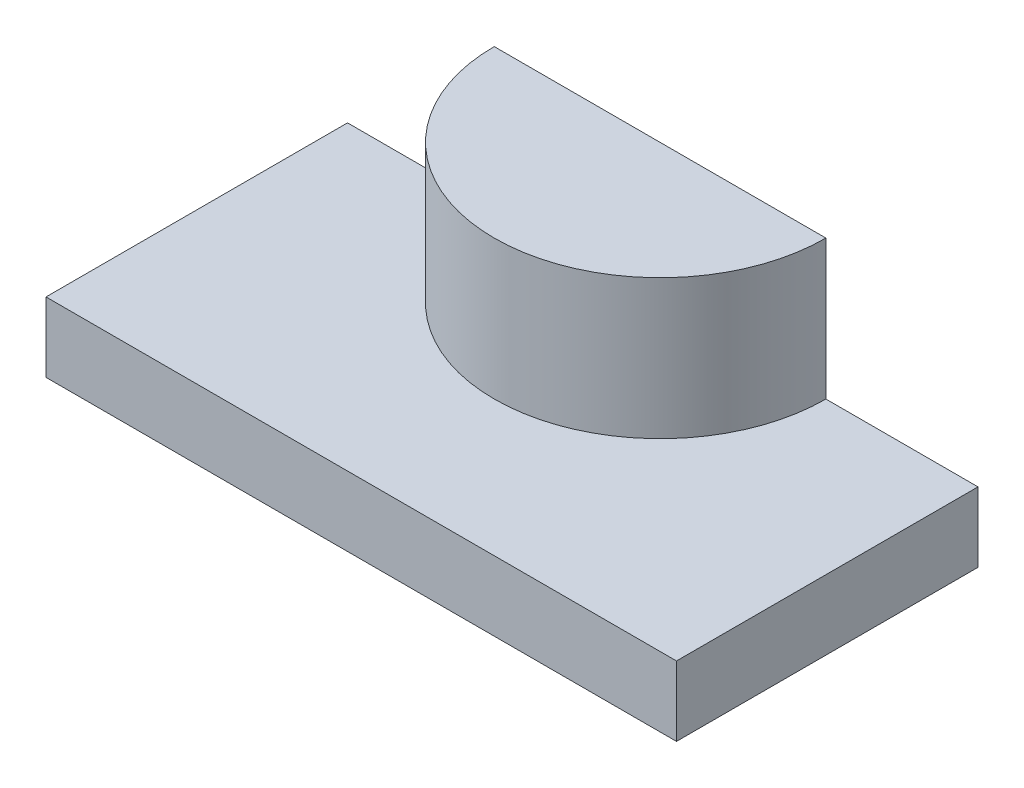
SolidWorks part; units mm, degrees
ref_plane "前视基准面" through (0, 0, 0) normal (0, 0, 1) x (1, 0, 0)
ref_plane "上视基准面" through (0, 0, 0) normal (0, 1, 0) x (1, 0, 0)
ref_plane "右视基准面" through (0, 0, 0) normal (1, 0, 0) x (0, 0, -1)
other "Configuration Table"
sketch "草图1" plane through (0, 0, 0) normal (0, 1, 0) x (1, 0, 0)
  line L1 (0, 0) -> (90.4507, 0)
  line L2 (0, 0) -> (0, 43.2552)
  line L3 (0, 43.2552) -> (90.4507, 43.2552)
  line L4 (90.4507, 0) -> (90.4507, 43.2552)
extrude "凸台-拉伸1" add sketch "草图1" along normal blind 10
sketch "草图2" plane through (0, 10, 0) normal (0, 1, 0) x (1, 0, 0)
  line L4 (0, 43.2552) -> (0, 0)
  line L5 (0, 0) -> (90.4507, 0)
  line L6 (90.4507, 0) -> (90.4507, 43.2552)
  line L7 (90.4507, 43.2552) -> (0, 43.2552)
  line L8 (0, 43.2552) -> (0, 0)
  line L9 (0, 0) -> (90.4507, 0)
  line L10 (90.4507, 0) -> (90.4507, 43.2552)
  line L11 (90.4507, 43.2552) -> (0, 43.2552)
  circle A0 centre (44.8388, 43.2552) radius 23.7914
  dimension "D1" = 0
extrude "凸台-拉伸2" add sketch "草图2" along normal blind 20 contours L11 A0 region at (44.8388, 10, -33.1578)
